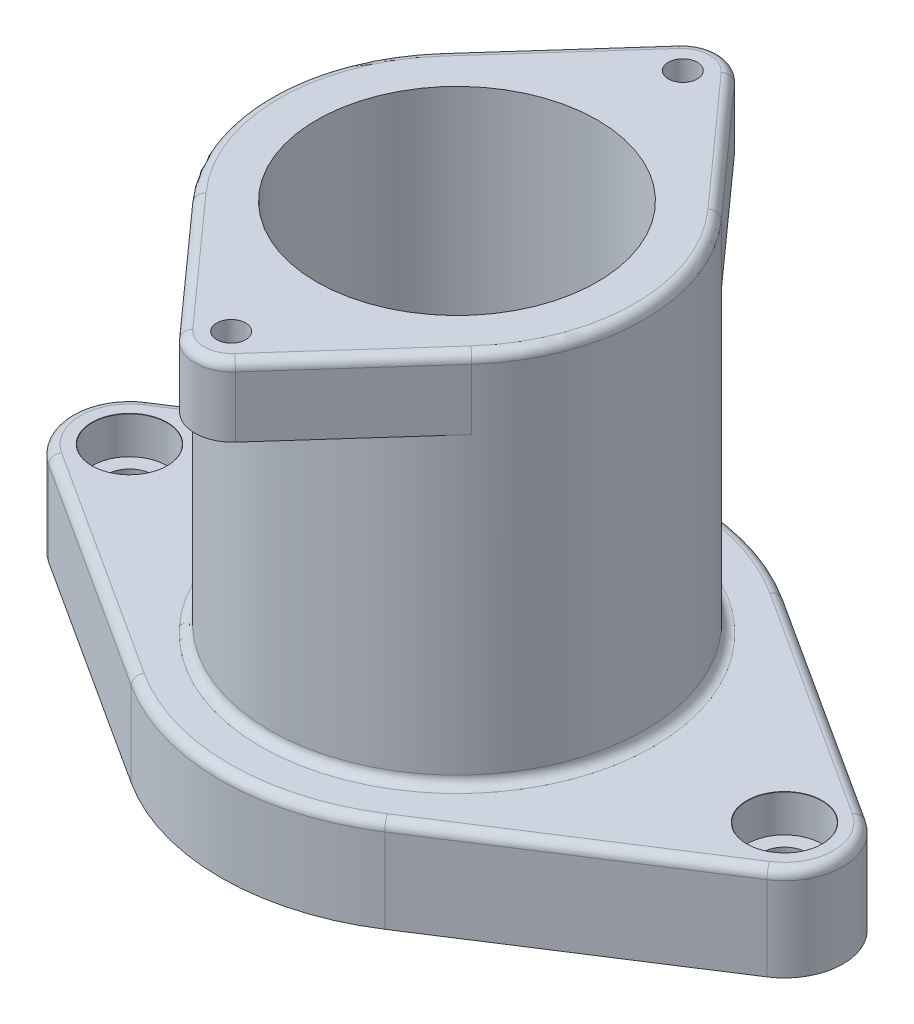
SolidWorks part; units mm, degrees
ref_plane "Front Plane" through (0, 0, 0) normal (0, 0, 1) x (1, 0, 0)
ref_plane "Top Plane" through (0, 0, 0) normal (0, 1, 0) x (1, 0, 0)
ref_plane "Right Plane" through (0, 0, 0) normal (1, 0, 0) x (0, 0, -1)
sketch "Sketch1" plane through (0, 0, 0) normal (0, 1, 0) x (1, 0, 0)
  line L0 (-965.3153, 0) -> (47300.4494, 0) construction
  line L1 (0, -965.3153) -> (0, 47300.4494) construction
  line L2 (-35, 0) -> (35, 0) construction
  line L3 (-38.3865, 5.253) -> (0, 30)
  line L4 (0, 30) -> (38.3865, 5.253)
  line L5 (0, -30) -> (38.3865, -5.253)
  line L6 (-38.3865, -5.253) -> (0, -30)
  line L7 (0, 24.13) -> (0, -24.13) construction
  line L8 (0, 30) -> (-14.9071, 13.3333)
  line L9 (0, 30) -> (14.9071, 13.3333)
  line L10 (0, -30) -> (14.9071, -13.3333)
  line L11 (0, -30) -> (-14.9071, -13.3333)
  line L12 (-7.5, 12.9904) -> (-7.5, -12.9904)
  line L13 (7.5, 12.9904) -> (7.5, -12.9904)
  circle A0 centre (0, 0) radius 15
  circle A1 centre (0, 0) radius 20
  circle A4 centre (-35, 0) radius 6.25
  circle A5 centre (35, 0) radius 6.25
  circle A6 centre (0, 24.13) radius 1.55
  circle A7 centre (0, -24.13) radius 1.55
  point P11 (-35, 0)
  point P13 (35, 0)
  point P14 (0, 0)
  point P18 (0, -24.13)
  point P24 (0, 0)
  point P25 (0, 24.13)
  dimension "D2" = 30
  dimension "D3" = 5
  dimension "D5" = 12.5
  dimension "D7" = 3.1
  dimension "D1" = 30
  dimension "D4" = 35
  dimension "D6" = 48.26
  dimension "D8" = 7.5
extrude "Boss-Extrude1" add sketch "Sketch1" against normal blind 10 contours A4 | A4 L6 L11 A1 L8 L3 | A1 A0 | A1 L9 L8 A6 | A6 | A5 L4 L9 A1 L10 L5 | A1 L11 L10 A7 | A7 | A5 region at (-20.7977, 0, 0) region at (-35, 0, 0) region at (0, 0, -22.3017) region at (20.7977, 0, 0) region at (35, 0, 0) region at (0, 0, -19.4343) region at (0, 0, 22.3017) region at (0, 0, -24.13) region at (0, 0, 24.13)
extrude "Boss-Extrude2" add sketch "Sketch1<3>" along normal blind 40 contours A1 A0 region at (0, 0, -19.4343)
sketch "Sketch1<3>" plane through (0, 0, 0) normal (0, 1, 0) x (1, 0, 0) same geometry as "Sketch1"
extrude "Boss-Extrude3" add sketch "Sketch1<4>" against normal blind 7.5 from surface contours A1 L9 L8 A6 | A1 L11 L10 A7 region at (0, 0, -22.3017) region at (0, 0, 22.3017) starting at face at (0, 40, 15)
sketch "Sketch1<4>" plane through (0, 0, 0) normal (0, 1, 0) x (1, 0, 0) same geometry as "Sketch1"
sketch "Sketch2" plane through (0, 0, 0) normal (0, 1, 0) x (1, 0, 0)
  point P0 (-35, 0)
  point P1 (35, 0)
hole_wizard "CBORE for M4 SHCS1" positions "Sketch2" profile "Sketch3" counterbore size "M4" standard "ANSI Metric"
sketch "Sketch3" plane through (-35, 0, 0) normal (1, 0, 0) x (0, 0, 1)
  line L0 (0, 0) -> (0, 11.4421)
  line L1 (0, 11.4421) -> (2.4, 10)
  line L2 (2.4, 10) -> (2.4, 4)
  line L3 (2.4, 4) -> (4, 4)
  line L5 (4, 4) -> (4, 0.025)
  line L6 (4, 0.025) -> (4.025, 0)
  line L7 (4.025, 0) -> (0, 0)
  line L8 (-4, 0.025) -> (-4.025, 0) construction
  line L10 (0, 11.4421) -> (-2.4, 10) construction
  line L11 (0, -6.35) -> (0, 107.95) construction
  dimension "Hole Dia." = 4.8
  dimension "Hole Depth" = 10
  dimension "C'Bore Dia." = 8
  dimension "C'Bore Depth" = 4
  dimension "Near C'Sink Dia." = 8.05
  dimension "Near C'Sink Angle" = 90
  dimension "Drill Angle" = 118
fillet "Fillet1" radius 25 2 edges at (0, -5, -30) (0, -5, 30)
fillet "Fillet3" radius 4 2 edges at (0, 36.25, -30) (0, 36.25, 30)
fillet "Fillet2" radius 1 17 edges at (-41.25, 0, 0) (-25.9663, 0, -13.2601) (0, 0, -25.2551) (25.9663, 0, -13.2601) (41.25, 0, 0) (25.9663, 0, 13.2601) (0, 0, 25.2551) (0, 0, 20) (-25.9663, 0, 13.2601) (-8.9443, 40, -20) (0, 40, -28) (8.9443, 40, -20) (20, 40, 0) (8.9443, 40, 20) (0, 40, 28) (-8.9443, 40, 20) (-20, 40, 0)
